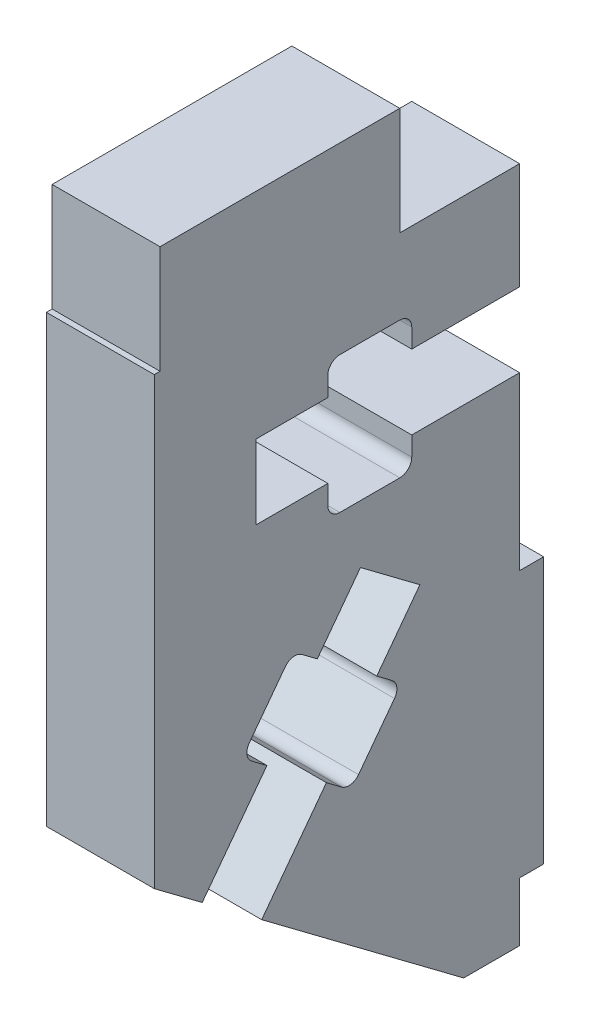
SolidWorks part; units mm, degrees
ref_plane "Front Plane" through (0, 0, 0) normal (0, 0, 1) x (1, 0, 0)
ref_plane "Top Plane" through (0, 0, 0) normal (0, 1, 0) x (1, 0, 0)
ref_plane "Right Plane" through (0, 0, 0) normal (1, 0, 0) x (0, 0, -1)
sketch "Sketch1" plane through (0, 0, 0) normal (1, 0, 0) x (0, 0, -1)
  line L0 (0, 0) -> (0, -30)
  line L1 (0, -30) -> (-40, 0)
  line L2 (-40, 0) -> (0, 0)
  dimension "D1" = 40
  dimension "D2" = 30
extrude "Boss-Extrude1" add sketch "Sketch1" along normal blind 4.5
sketch "Sketch2" plane through (4.5, 0, 0) normal (1, 0, 0) x (0, 0, -1)
  line L0 (0, -25.8) -> (1, -25.8)
  line L1 (0, -30) -> (0, 0) construction
  line L2 (1, -25.8) -> (1, -14.7)
  line L3 (1, -14.7) -> (0, -14.7)
  line L4 (0, -14.7) -> (0, -25.8)
  line L5 (1, -20.25) -> (0, -20.25) construction
  line L6 (0, -14.75) -> (4.5, -14.75) construction
  line L7 (0, -25.75) -> (4.5, -25.75) construction
  dimension "D2" = 1
  dimension "D3" = 0.05
  dimension "D1" = 0.05
extrude "Boss-Extrude2" add sketch "Sketch2" against normal through all
sketch "Sketch3" plane through (4.5, 0, 0) normal (1, 0, 0) x (0, 0, -1)
  line L0 (0, -6) -> (-11, -6) construction
  line L1 (0, -14.7) -> (0, 0) construction
  line L2 (-11, -7.55) -> (-11, -4.45) construction
  line L3 (-11, -4.45) -> (0, -4.45) construction
  line L4 (0, -4.45) -> (-4.5, -4.45)
  line L5 (-4.5, -4.45) -> (-4.5, -3.65)
  line L6 (-5, -3.15) -> (-7.5, -3.15)
  line L7 (-8, -3.65) -> (-8, -4.45)
  line L8 (-8, -4.45) -> (-11, -4.45)
  line L9 (-11, -4.45) -> (-11, -7.55)
  line L10 (0, -4.45) -> (0, -7.55)
  line L12 (-11, -7.55) -> (0, -7.55) construction
  line L13 (-8, -7.55) -> (-11, -7.55)
  line L14 (-8, -8.35) -> (-8, -7.55)
  line L15 (-5, -8.85) -> (-7.5, -8.85)
  line L16 (-4.5, -7.55) -> (-4.5, -8.35)
  line L17 (0, -7.55) -> (-4.5, -7.55)
  arc A0 (-4.5, -3.65) -> (-5, -3.15) centre (-5, -3.65) ccw
  arc A1 (-7.5, -3.15) -> (-8, -3.65) centre (-7.5, -3.65) ccw
  arc A2 (-7.5, -8.85) -> (-8, -8.35) centre (-7.5, -8.35) cw
  arc A3 (-4.5, -8.35) -> (-5, -8.85) centre (-5, -8.35) cw
  point P15 (-4.5, -3.15)
  point P18 (-8, -3.15)
  point P29 (-8, -8.85)
  point P30 (-4.5, -8.85)
  dimension "D7" = 0.5
  dimension "D1" = 11
  dimension "D2" = 1.55
  dimension "D3" = 3.5
  dimension "D4" = 2.85
  dimension "D5" = 8
  dimension "D6" = 6
extrude "Cut-Extrude1" cut sketch "Sketch3" against normal through all
sketch "Sketch4" plane through (4.5, 0, 0) normal (1, 0, 0) x (0, 0, -1)
  line L0 (-13.24, -20.07) -> (-6.64, -11.27) construction
  line L1 (-40, 0) -> (0, -30) construction
  line L2 (-6.64, -11.27) -> (-4.16, -13.13) construction
  line L3 (-5.4, -12.2) -> (-12, -21) construction
  line L4 (-10.76, -21.93) -> (-13.24, -20.07)
  line L5 (-13.24, -20.07) -> (-10.54, -16.47)
  line L6 (-10.54, -16.47) -> (-11.18, -15.99)
  line L7 (-11.28, -15.29) -> (-9.78, -13.29)
  line L8 (-9.08, -13.19) -> (-8.44, -13.67)
  line L9 (-8.44, -13.67) -> (-6.64, -11.27)
  line L10 (-6.64, -11.27) -> (-4.16, -13.13)
  line L11 (0, 0) -> (-40, 0) construction
  line L12 (-10.76, -21.93) -> (-4.16, -13.13) construction
  line L13 (-5.96, -15.53) -> (-4.16, -13.13)
  line L14 (-5.32, -16.01) -> (-5.96, -15.53)
  line L15 (-6.72, -18.71) -> (-5.22, -16.71)
  line L16 (-8.06, -18.33) -> (-7.42, -18.81)
  line L17 (-10.76, -21.93) -> (-8.06, -18.33)
  arc A0 (-11.18, -15.99) -> (-11.28, -15.29) centre (-10.88, -15.59) cw
  arc A1 (-9.78, -13.29) -> (-9.08, -13.19) centre (-9.38, -13.59) cw
  arc A2 (-5.22, -16.71) -> (-5.32, -16.01) centre (-5.62, -16.41) ccw
  arc A3 (-7.42, -18.81) -> (-6.72, -18.71) centre (-7.12, -18.41) ccw
  point P14 (-11.58, -15.69)
  point P17 (-9.48, -12.89)
  point P28 (-4.92, -16.31)
  point P29 (-7.02, -19.11)
  dimension "D7" = 0.5
  dimension "D1" = 11
  dimension "D2" = 1.55
  dimension "D3" = 3.5
  dimension "D4" = 2.85
  dimension "D5" = 8
  dimension "D6" = 21
extrude "Cut-Extrude2" cut sketch "Sketch4" against normal through all
sketch "Sketch5" plane through (4.5, 0, 0) normal (1, 0, 0) x (0, 0, -1)
  line L0 (-15.24, -18.57) -> (-15.24, 0)
  line L1 (-40, 0) -> (-13.24, -20.07) construction
  line L2 (0, 0) -> (-40, 0) construction
  line L3 (-15.24, 0) -> (-40, 0)
  line L4 (-40, 0) -> (-15.24, -18.57)
  dimension "D1" = 2
extrude "Cut-Extrude3" cut sketch "Sketch5" against normal through all
sketch "Sketch6" plane through (0, 0, 11) normal (0, 0, -1) x (-1, 0, 0)
  line L0 (-2.25, -4.45) -> (-2.25, -7.55) construction
  line L1 (0, -4.45) -> (-4.5, -4.45) construction
  line L2 (0, -7.55) -> (-4.5, -7.55) construction
  circle A0 centre (-2.25, -6) radius 1.5
  dimension "D1" = 3
sketch "Sketch7" plane through (0, -10.4, 7.8) normal (0, -0.8, 0.6) x (1, 0, 0)
  line L0 (2.25, -1.45) -> (2.25, -4.55) construction
  line L1 (0, -1.45) -> (4.5, -1.45) construction
  line L2 (0, -4.55) -> (4.5, -4.55) construction
  circle A0 centre (2.25, -3) radius 1.55
sketch "Sketch8" plane through (4.5, 0, 0) normal (1, 0, 0) x (0, 0, -1)
  line L0 (-10, 4.5) -> (-10, 0) construction
  line L1 (-15, 0) -> (-5, 0)
  line L2 (-15, 0) -> (-15, 4.5)
  line L3 (-15, 4.5) -> (-5, 4.5)
  line L4 (-5, 0) -> (-5, 4.5)
  line L5 (0, 0) -> (-15.24, 0) construction
  dimension "D1" = 10
  dimension "D2" = 4.5
  dimension "D3" = 10
extrude "Boss-Extrude3" add sketch "Sketch8" against normal through all
sketch "Sketch10" plane through (4.5, 0, 0) normal (1, 0, 0) x (0, 0, -1)
  line L0 (0, -28.25) -> (-2.3333, -28.25)
  line L1 (0, -30) -> (0, -25.8) construction
  line L2 (-10.76, -21.93) -> (0, -30) construction
  line L3 (-2.3333, -28.25) -> (0, -30)
  line L4 (0, -30) -> (0, -28.25)
  dimension "D1" = 0
extrude "Cut-Extrude4" cut sketch "Sketch10" against normal through all contours L0 L3 L4
equation "\"X-ROD-SPACING\"=45"
equation "\"Y-ROD-SPACING\"=75"
equation "\"Z-ROD-SPACING\"=17.5"
equation "\"Y-BED-OFFSET\"=2"
equation "\"Y-BED-ROD-INSET\"=3.5"
equation "\"Y-BED-SCREW-SPACING\"=209"
equation "\"Y-BED-SCREW-CUTOUT-SLOT-HEIGHT\"=2"
equation "\"T-SLOT-NUT-FILLET-RADIUS\"=0.5"
equation "\"T-SLOT-SCREW-SHAFT-RADIUS\"=1.55"
equation "\"T-SLOT-SCREW-SHAFT-CUTOUT-LENGTH\"=11.0"
equation "\"T-SLOT-NUT-DEPTH\"=3.5"
equation "\"T-SLOT-NUT-WIDTH\"=2.85"
equation "\"T-SLOT-NUT-END-DISTANCE\"=8"
equation "\"ACRYLIC-THICKNESS\"=10"
equation "\"ACRYLIC-THICKNESS2\"=4.5"
equation "\"ACRYLIC-TAB-CUTOUT-SIZE\"=\"ACRYLIC-THICKNESS\"+\"ACRYLIC-TAB-TOLERANCE\"*2"
equation "\"ACRYLIC-TAB-TOLERANCE\"=-.05"
equation "\"ACRYLIC-TAB-WIDTH\"=\"ACRYLIC-THICKNESS\""
equation "\"ACRYLIC-M3-HOLE\"=2.9"
equation "\"SMOOTHROD-CAP-SCREW-DISTANCE\"=20"
equation "\"FRAME-WIDTH-INNER\"=370"
equation "\"NEMA17-HOLE-SPACING\"=31"
equation "\"NEMA17-CENTRAL-CUTOUT\"=22.5"
equation "\"Z-BRACKET-REACH\"=55"
equation "\"Z-ROD-INSET\"=16"
equation "\"TOP-BRACKET-SPACING\"=40"
equation "\"SMOOTHROD-X-LENGTH\"=350"
equation "\"SMOOTHROD-Y-LENGTH\"=350"
equation "\"SMOOTHROD-Z-LENGTH\"=350"
equation "\"SMOOTHROD-TIGHTENING-HEADROOM\"=.25"
equation "\"LEADSCREW-Z-LENGTH\"=300"
equation "\"SCREW-LENGTH-FRAME\"=\"ACRYLIC-THICKNESS\" + 10"
equation "\"SCREW-LENGTH-MOTOR\"=\"ACRYLIC-THICKNESS\" + 5"
equation "\"SCREW-LENGTH-EXTRUDER\"=28"
equation "\"SCREW-HEAD-RADIUS\"=6"
equation "\"PRINTED-M3-HOLE\"=3.5"
equation "\"PRINTED-X-SMOOTHROD-DIAMETER\"=8.4"
equation "\"PRINTED-X-SMOOTHROD-CUTOUT\"=10"
equation "\"PRINTED-X-BASE-HEIGHT\"=10"
equation "\"PRINTED-LM8UU-CUTOUT-SIZE\"=15.5"
equation "\"PRINTED-LM8UU-CUTOUT-LENGTH\"=24.5"
equation "\"PRINTED-X-IDLER-HEIGHT\"=16"
equation "\"PRINTED-M3-NUT-AF\"=6.25"
equation "\"PSU-MOUNTING-WIDTH\"=95"
equation "\"PSU-MOUNTING-HEIGHT\"=177"
equation "\"Y-BELT-TO-ROD-DISTANCE\"=20"
equation "\"SPOOL-HOLDER-ROD-SPACING\"=150"
equation "\"ACRYLIC-X-CARRIAGE-WIDTH\"=55"
equation "\"ACRYLIC-X-CARRIAGE-HEIGHT\"=75"
equation "\"ACRYLIC-X-CARRIAGE-LM8UU-CUTOUT-WIDTH\"=24.25"
equation "\"ACRYLIC-X-CARRIAGE-LM8UU-CUTOUT-HEIGHT\"=11.0"
equation "\"ACRYLIC-X-CARRIAGE-SCREW-SPACING-X\"=15"
equation "\"ACRYLIC-X-CARRIAGE-SCREW-SPACING-Y\"=33"
equation "\"ACRYLIC-X-CARRIAGE-CENTER-TAB-SPACING\"=14"
equation "\"ACRYLIC-X-CARRIAGE-EXTRUDER-OFFSET\"=26"
equation "\"ACRYLIC-X-CARRIAGE-EXTRUDER-ANGLE\"=90"
equation "\"ACRYLIC-X-CARRIAGE-EXTRUDER-SHELF-DEPTH\"=\"ACRYLIC-X-CARRIAGE-EXTRUDER-OFFSET\" + 28"
equation "\"ACRYLIC-X-CARRIAGE-EXTRUDER-BRACE-SPACING\"=23"
equation "\"ACRYLIC-X-CARRIAGE-EXTRUDER-BRACE-TAB-OFFSET\"=20"
equation "\"ACRYLIC-X-CARRIAGE-EXTRUDER-BRACE-HEIGHT\"=35"
equation "\"ACRYLIC-X-CARRIAGE-EXTRUDER-BRACE-SCREW-SPACING\"=22"
equation "\"ACRYLIC-X-CARRIAGE-DUAL-WIDTH-MULTIPLIER\"=1.65"
equation "\"ACRYLIC-X-CARRIAGE-DUAL-HOTEND-SPACING\"=42"
equation "\"ACRYLIC-X-CARRIAGE-DUAL-WIDTH\"=75"
equation "\"ACRYLIC-X-CARRIAGE-DUAL-FAN-OFFSET\"=52"
equation "\"ACRYLIC-X-CARRIAGE-DUAL-FAN-HEIGHT\"=20"
equation "\"ACRYLIC-X-CARRIAGE-DUAL-HOTEND-SEPARATION\"=36"
equation "\"ACRYLIC-X-CARRIAGE-DUAL-MOUNT-PLATE-DEPTH\"=75"
equation "\"ACRYLIC-X-CARRIAGE-DUAL-MOUNT-BRACE-WIDTH\"=33"
equation "\"ACRYLIC-X-CARRIAGE-DUAL-MOUNT-SCREW-WIDTH\"=40"
equation "\"BLOWER-FAN-WIDTH\"=15"
equation "\"D1@Boss-Extrude1\"=\"ACRYLIC-THICKNESS2\""
equation "\"D1@Sketch2\"=\"ACRYLIC-TAB-TOLERANCE\""
equation "\"D1@Sketch3\"=\"T-SLOT-SCREW-SHAFT-CUTOUT-LENGTH\""
equation "\"D2@Sketch3\"=\"T-SLOT-SCREW-SHAFT-RADIUS\""
equation "\"D3@Sketch3\"=\"T-SLOT-NUT-DEPTH\""
equation "\"D4@Sketch3\"=\"T-SLOT-NUT-WIDTH\""
equation "\"D5@Sketch3\"=\"T-SLOT-NUT-END-DISTANCE\""
equation "\"D7@Sketch3\"=\"T-SLOT-NUT-FILLET-RADIUS\""
equation "\"D1@Sketch4\"=\"T-SLOT-SCREW-SHAFT-CUTOUT-LENGTH\""
equation "\"D2@Sketch4\"=\"T-SLOT-SCREW-SHAFT-RADIUS\""
equation "\"D3@Sketch4\"=\"T-SLOT-NUT-DEPTH\""
equation "\"D4@Sketch4\"=\"T-SLOT-NUT-WIDTH\""
equation "\"D5@Sketch4\"=\"T-SLOT-NUT-END-DISTANCE\""
equation "\"D7@Sketch4\"=\"T-SLOT-NUT-FILLET-RADIUS\""
equation "\"D1@Sketch8\"=\"ACRYLIC-TAB-WIDTH\""
equation "\"D2@Sketch8\"=\"ACRYLIC-THICKNESS2\""
equation "\"D3@Sketch2\"=\"ACRYLIC-TAB-TOLERANCE\""
